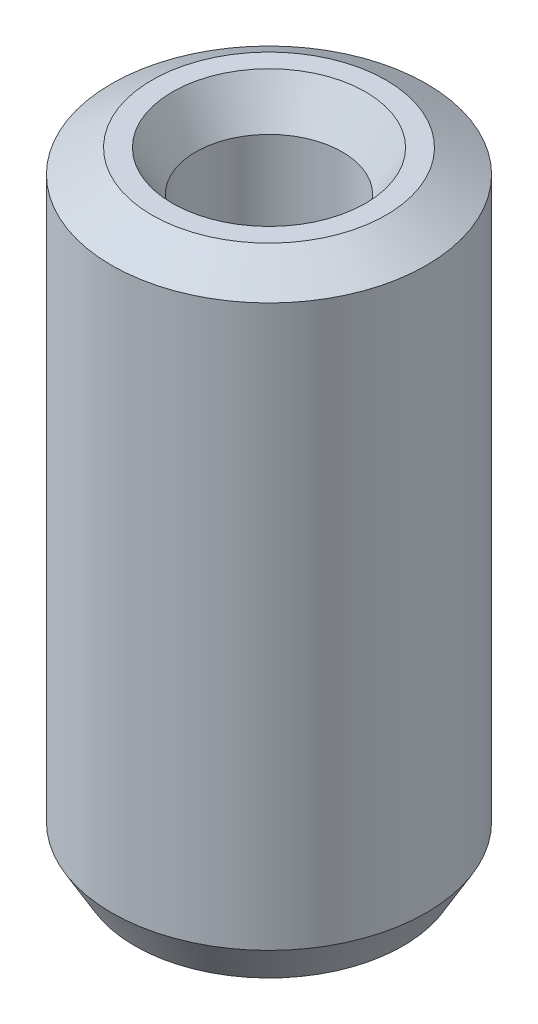
SolidWorks part; units mm, degrees
ref_plane "Front Plane" through (0, 0, 0) normal (0, 0, 1) x (1, 0, 0)
ref_plane "Top Plane" through (0, 0, 0) normal (0, 1, 0) x (1, 0, 0)
ref_plane "Right Plane" through (0, 0, 0) normal (1, 0, 0) x (0, 0, -1)
sketch "Sketch1" plane through (0, 0, 0) normal (0, 1, 0) x (1, 0, 0)
  circle A0 centre (0, 0) radius 5
  dimension "SLEEVE_OD" = 10
extrude "Boss-Extrude1" add sketch "Sketch1" along normal blind 19.8357
sketch "Sketch2" plane through (0, 0, 0) normal (0, 1, 0) x (1, 0, 0)
  circle A0 centre (0, 0) radius 2.3283
  dimension "BORE_D" = 4.6566
extrude "Cut-Extrude1" cut sketch "Sketch2" along normal through all
chamfer "Chamfer1" distance 0.7402 angle 60 4 edges at (0, 19.8357, 2.3283) (0, 0, 2.3283) (0, 0, 5) (0, 19.8357, 5) first distance on face at (0, 19.8357, 2.3283) first distance on face at (0, 0, 2.3283) first distance on face at (0, 19.8357, 5)
